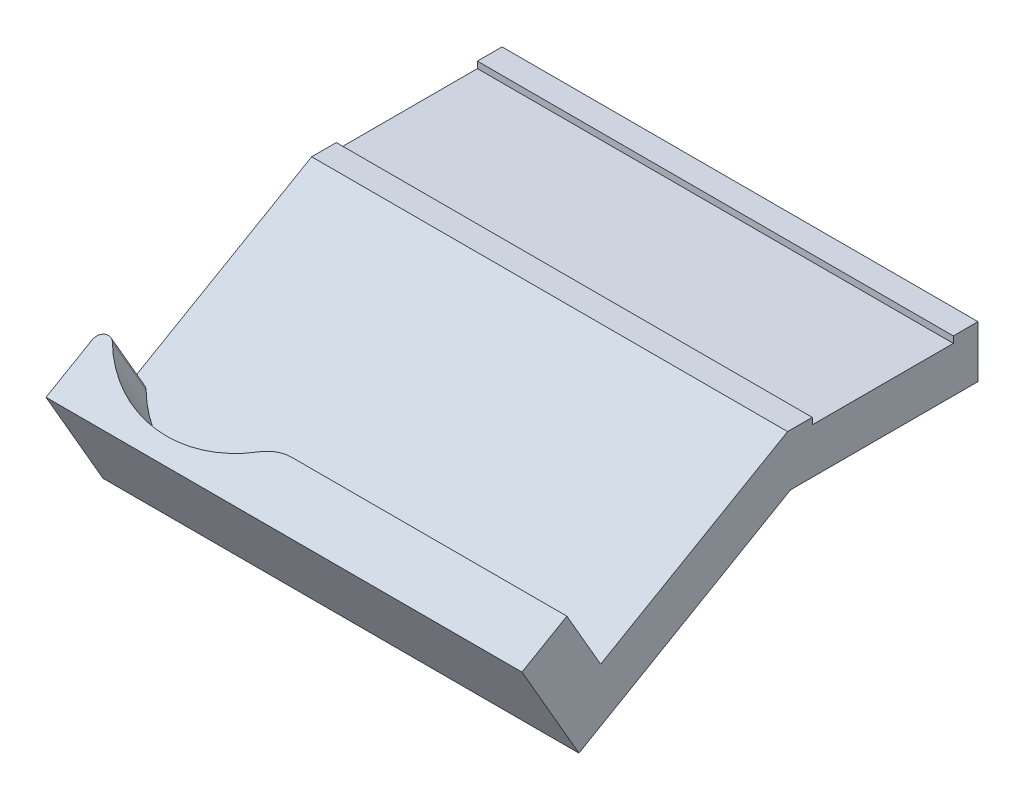
SolidWorks part; units mm, degrees
ref_plane "Front Plane" through (0, 0, 0) normal (0, 0, 1) x (1, 0, 0)
ref_plane "Top Plane" through (0, 0, 0) normal (0, 1, 0) x (1, 0, 0)
ref_plane "Right Plane" through (0, 0, 0) normal (1, 0, 0) x (0, 0, -1)
sketch "Sketch1" plane through (0, 0, 0) normal (0, 1, 0) x (1, 0, 0)
  line L1 (0, 33.9) -> (55, 33.9)
  line L2 (0, 33.9) -> (0, 0)
  line L3 (0, 0) -> (55, 0)
  line L4 (55, 33.9) -> (55, 0)
  dimension "D1" = 55
  dimension "D2" = 33.9
extrude "Boss-Extrude1" add sketch "Sketch1" along normal blind 50 contours L2 L3 L4 L1
sketch "Sketch4" plane through (55, 0, 0) normal (1, 0, 0) x (0, 0, -1)
  line L0 (33.9, 0) -> (0, 0) construction
  line L1 (-18.6, 53.3013) -> (24.7013, 78.3013)
  line L2 (-18.6, 53.3013) -> (6.4, 10)
  line L3 (6.4, 10) -> (49.7013, 35)
  line L4 (24.7013, 78.3013) -> (49.7013, 35)
  line L5 (0, 50) -> (0, 0) construction
  dimension "D1" = 50
  dimension "D2" = 50
  dimension "D3" = 10
  dimension "D4" = 6.4
  dimension "D5" = 30
extrude "Cut-Extrude1" cut sketch "Sketch4" against normal blind 50
sketch "Sketch5" plane through (55, 0, 0) normal (1, 0, 0) x (0, 0, -1)
  line L0 (0, 21.0851) -> (0, 0) construction
  line L1 (-11.1603, 20.4153) -> (-2.5, 25.4153)
  line L2 (-11.1603, 20.4153) -> (-6.1603, 11.755)
  line L3 (-6.1603, 11.755) -> (2.5, 16.755)
  line L4 (-2.5, 25.4153) -> (2.5, 16.755)
  line L5 (0, 21.0851) -> (6.4, 10) construction
  dimension "D1" = 10
  dimension "D2" = 10
  dimension "D3" = 2.5
extrude "Cut-Extrude2" cut sketch "Sketch5" against normal through all
sketch "Sketch12" plane through (55, 0, 0) normal (1, 0, 0) x (0, 0, -1)
  line L0 (2.5, 16.755) -> (6.4, 10)
  line L1 (6.4, 10) -> (7.7943, 10.805)
  line L2 (6.4, 10) -> (33.9, 25.8771) construction
  line L3 (7.7943, 10.805) -> (3.8943, 17.56)
  line L4 (3.8943, 17.56) -> (2.5, 16.755)
  dimension "D1" = 1.61
extrude "Boss-Extrude2" add sketch "Sketch12" against normal through all contours L3 L4 L0 L1
sketch "Sketch6" plane through (0, 4.7287, 2.7301) normal (0, 0.866, 0.5) x (1, 0, 0)
  line L0 (55, 7.6558) -> (0, 7.6558) construction
  line L3 (0, 54.3583) -> (0, 25) construction
  circle A0 centre (12, 22.1558) radius 13.75
  dimension "D1" = 27.5
  dimension "D2" = 14.5
  dimension "D3" = 12
extrude "Cut-Extrude3" cut sketch "Sketch6" along normal through all
ref_axis "Axis2" through (12, 43.8187, -0.2846) along (0, -0.866, -0.5)
sketch "Sketch7" plane through (55, 0, 0) normal (1, 0, 0) x (0, 0, -1)
  line L0 (0, 15.3116) -> (6.7439, 19.2052)
  line L1 (22.2709, 19.1631) -> (10.6439, 12.4502) construction
  line L2 (6.7439, 19.2052) -> (10.6439, 12.4502)
  line L3 (10.6439, 12.4502) -> (102.2025, 65.3116)
  line L4 (102.2025, 65.3116) -> (25.4084, 65.3116)
  line L5 (25.4084, 65.3116) -> (0, 65.3116)
  line L6 (0, 65.3116) -> (0, 15.3116)
  line L7 (10.6439, 12.4502) -> (0, 30.8859) construction
  line L8 (7.7943, 10.805) -> (33.9, 25.8771) construction
  dimension "D1" = 50
extrude "Cut-Extrude4" cut sketch "Sketch7" against normal through all contours L5 L6 L0 L2 L3 L4
sketch "Sketch8" plane through (0, 0, 0) normal (0, 1, 0) x (1, 0, 0)
  line L0 (12, 0.2846) -> (12, 11.9021) construction
  line L3 (55, 33.9) -> (0, 33.9) construction
  circle A0 centre (25.75, 35.4) radius 6
  dimension "D1" = 12
  dimension "D3" = 1.5
  dimension "D2" = 13.75
extrude "Cut-Extrude5" cut sketch "Sketch8" along normal through all contours A0
sketch "Sketch9" plane through (55, 0, 0) normal (1, 0, 0) x (0, 0, -1)
  line L0 (29.4, 23.2791) -> (33.9, 23.2791)
  line L1 (33.9, 25.8771) -> (33.9, 0) construction
  line L2 (33.9, 23.2791) -> (33.9, 25.8771)
  line L3 (33.9, 25.8771) -> (29.4, 23.2791)
extrude "Cut-Extrude6" cut sketch "Sketch9" against normal through all
sketch "Sketch10" plane through (0, 0, 0) normal (0, 1, 0) x (1, 0, 0)
  line L0 (0, 29.4) -> (25.75, 29.4) construction
  line L1 (55, 29.4) -> (0, 29.4)
  line L2 (55, 29.4) -> (55, 33.9)
  line L3 (55, 33.9) -> (0, 33.9)
  line L4 (0, 29.4) -> (0, 33.9)
  line L5 (0, 29.4) -> (0, 10.6439) construction
extrude "Cut-Extrude7" cut sketch "Sketch10" along normal through all
fillet "Fillet5" radius 1 1 edges at (0, 15.8277, -8.6939) tangent propagation no
fillet "Fillet6" radius 5 1 edges at (21.4338, 14.1825, -5.8443)
sketch "Sketch16" plane through (55, 0, 0) normal (1, 0, 0) x (0, 0, -1)
  line L0 (29.4, 17.0791) -> (6.5847, 3.9066)
  line L1 (29.4, 23.2791) -> (29.4, 0) construction
  line L2 (6.5847, 3.9066) -> (0, 15.3116)
  line L3 (0, 15.3116) -> (0, 0)
  line L4 (0, 0) -> (29.4, 0)
  line L5 (29.4, 0) -> (29.4, 17.0791)
  line L6 (7.7943, 10.805) -> (29.4, 23.2791) construction
  line L7 (29.4, 0) -> (0, 0) construction
  dimension "D1" = 6.2
extrude "Cut-Extrude8" cut sketch "Sketch16" against normal through all
sketch "Sketch17" plane through (0, 0, -29.4) normal (0, 0, -1) x (-1, 0, 0)
  line L1 (-55, 23.2791) -> (0, 23.2791)
  line L2 (-55, 23.2791) -> (-55, 17.2791)
  line L3 (-55, 17.2791) -> (0, 17.2791)
  line L4 (0, 23.2791) -> (0, 17.2791)
  dimension "D1" = 6
extrude "Boss-Extrude4" add sketch "Sketch17" along normal blind 22
sketch "Sketch18" plane through (55, 0, 0) normal (1, 0, 0) x (0, 0, -1)
  line L0 (17.9923, 10.4928) -> (40.1387, 23.2791)
  line L1 (29.4, 17.0791) -> (6.5847, 3.9066) construction
  line L2 (51.4, 23.2791) -> (29.4, 23.2791) construction
  line L3 (40.1387, 23.2791) -> (29.4, 23.2791)
  line L4 (29.4, 23.2791) -> (15.3077, 15.1428)
  line L5 (7.7943, 10.805) -> (29.4, 23.2791) construction
  line L6 (15.3077, 15.1428) -> (17.9923, 10.4928)
extrude "Boss-Extrude5" add sketch "Sketch18" against normal up to surface (55 mm away) contours L0 L3 L4 L6 up to face at (0, 16.2284, -24.5088)
sketch "Sketch19" plane through (0, 23.2791, 0) normal (0, 1, 0) x (1, 0, 0)
  line L0 (0, 51.4) -> (0, 29.4) construction
  line L1 (0, 48.55) -> (55, 48.55)
  line L2 (0, 48.55) -> (0, 32.25)
  line L3 (0, 32.25) -> (55, 32.25)
  line L4 (55, 48.55) -> (55, 32.25)
  line L5 (55, 51.4) -> (55, 29.4) construction
  point P8 (0, 40.4)
  dimension "D1" = 16.3
extrude "Cut-Extrude9" cut sketch "Sketch19" against normal blind 0.75
sketch "Sketch20" plane through (55, 0, 0) normal (1, 0, 0) x (0, 0, -1)
  line L0 (0, 15.3116) -> (-1.299, 14.5616)
  line L1 (-1.299, 14.5616) -> (5.2856, 3.1566)
  line L2 (5.2856, 3.1566) -> (6.5847, 3.9066)
  line L3 (6.5847, 3.9066) -> (0, 15.3116)
  line L4 (0, 15.3116) -> (3.8943, 17.56) construction
  line L5 (29.7464, 17.2791) -> (6.5847, 3.9066) construction
  dimension "D1" = 1.5
extrude "Boss-Extrude6" add sketch "Sketch20" against normal up to surface (55 mm away) contours L1 L2 L3 L0 up to face at (0, 18.3744, -29.4127)
